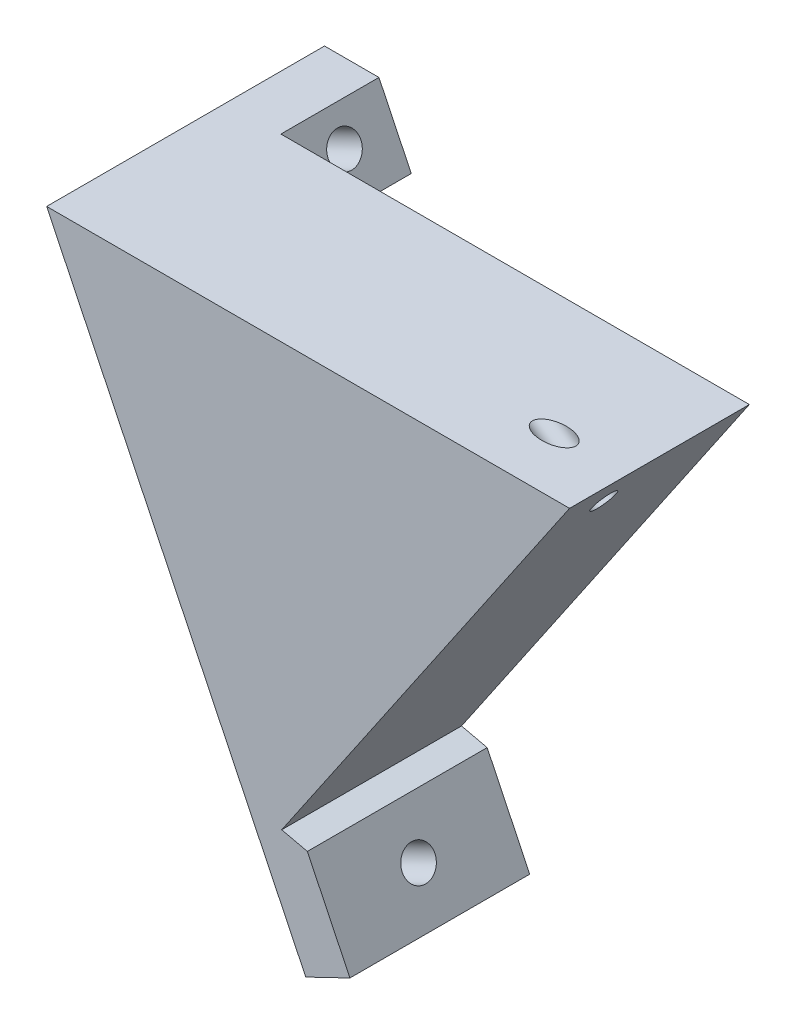
SolidWorks part; units mm, degrees
material "ABS"
ref_plane "Front Plane" through (0, 0, 0) normal (0, 0, 1) x (1, 0, 0)
ref_plane "Top Plane" through (0, 0, 0) normal (0, 1, 0) x (1, 0, 0)
ref_plane "Right Plane" through (0, 0, 0) normal (1, 0, 0) x (0, 0, -1)
sketch "Sketch1" plane through (0, 0, 0) normal (0, 0, 1) x (1, 0, 0)
  line L0 (-36.2386, 24.2413) -> (-9.7428, -30.7587)
  line L1 (-9.7428, -30.7587) -> (27.7446, 24.2413)
  line L2 (27.7446, 24.2413) -> (-36.2386, 24.2413)
  dimension "D1" = 55
  dimension "D2" = 55
  dimension "D3" = 60
extrude "Boss-Extrude1" add sketch "Sketch1" along normal blind 22
sketch "Sketch6" plane through (-19.9343, -9.6032, 0) normal (-0.9009, -0.434, 0) x (0, 0, 1)
  line L0 (22, 37.5671) -> (22, -23.4823) construction
  line L1 (0, 37.5671) -> (-12, 37.5671)
  line L2 (0, 37.5671) -> (0, 25.5671)
  line L3 (0, 25.5671) -> (-12, 25.5671)
  line L4 (-12, 37.5671) -> (-12, 25.5671)
  line L5 (0, -23.4823) -> (22, -23.4823)
  line L6 (0, -23.4823) -> (0, -35.4823)
  line L7 (0, -35.4823) -> (22, -35.4823)
  line L8 (22, -23.4823) -> (22, -35.4823)
  dimension "D1" = 12
  dimension "D2" = 12
  dimension "D3" = 0
  dimension "D4" = 12
extrude "Boss-Extrude4" add sketch "Sketch6" against normal blind 6
sketch "Sketch8" plane through (0, 0, 0) normal (0, 0, -1) x (-1, 0, 0)
  line L0 (9.7428, -30.7587) -> (4.3373, -28.1546)
  line L1 (4.3373, -28.1546) -> (7.4748, -27.4313)
  line L2 (9.7428, -30.7587) -> (-27.7446, 24.2413) construction
  line L3 (7.4748, -27.4313) -> (9.7428, -30.7587)
extrude "Boss-Extrude5" add sketch "Sketch8" against normal up to vertex (22 mm away) up to point (-9.7428, -30.7587, 22)
sketch "Sketch9" plane through (-14.5288, -6.9992, 0) normal (0.9009, 0.434, 0) x (0, 0, -1)
  line L2 (12, 25.5671) -> (0, 25.5671) construction
  line L3 (0, -35.4823) -> (-22, -35.4823) construction
  line L4 (-22, -35.4823) -> (-22, -23.4823) construction
  circle A0 centre (6, 30.5671) radius 2
  circle A1 centre (-11, -29.4823) radius 2
  point P9 (6, 25.5671)
  point P12 (-11, -35.4823)
  point P15 (-22, -29.4823)
  dimension "D1" = 4
  dimension "D2" = 4
  dimension "D3" = 5
  dimension "D4" = 0
  dimension "D5" = 0
  dimension "D6" = 0
extrude "Cut-Extrude9" cut sketch "Sketch9" against normal blind 6
sketch "Sketch10" plane through (7.6623, -5.2226, 0) normal (0.8263, -0.5632, 0) x (0, 0, -1)
  line L0 (-22, 35.657) -> (0, 35.657) construction
  line L2 (-22, -26.8768) -> (-22, 35.657) construction
  circle A0 centre (-15, 30.657) radius 1.5
  dimension "D1" = 3
  dimension "D2" = 5
  dimension "D3" = 7
extrude "Cut-Extrude10" cut sketch "Sketch10" against normal blind 36
sketch "Sketch11" plane through (0, 0, 0) normal (0, 0, 1) x (1, 0, 0)
  line L0 (-36.2386, 24.2413) -> (-29.5787, 24.2413)
  line L1 (-29.5787, 24.2413) -> (-30.8332, 26.8454)
  line L2 (-30.8332, 26.8454) -> (-36.2386, 24.2413)
extrude "Cut-Extrude11" cut sketch "Sketch11" against normal blind 36
